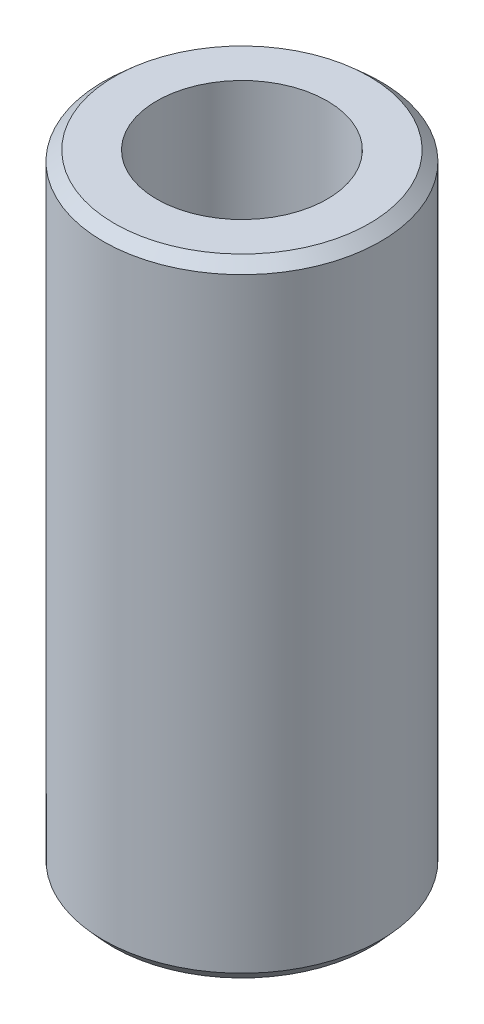
SolidWorks part; units mm, degrees
ref_plane "Front Plane" through (0, 0, 0) normal (0, 0, 1) x (1, 0, 0)
ref_plane "Top Plane" through (0, 0, 0) normal (0, 1, 0) x (1, 0, 0)
ref_plane "Right Plane" through (0, 0, 0) normal (1, 0, 0) x (0, 0, -1)
sketch "Sketch1" plane through (0, 0, 0) normal (0, 1, 0) x (1, 0, 0)
  circle A0 centre (0, 0) radius 20
  dimension "SHAFT_OD" = 40
extrude "Boss-Extrude1" add sketch "Sketch1" along normal blind 90.3574
sketch "Sketch2" plane through (0, 0, 0) normal (0, 1, 0) x (1, 0, 0)
  circle A0 centre (0, 0) radius 12.2946
  dimension "BORE_D" = 24.5892
extrude "Cut-Extrude1" cut sketch "Sketch2" along normal through all
chamfer "Chamfer1" distance 1.4382 angle 48.24 2 edges at (0, 90.3574, 20) (0, 0, 20) first distance on face at (0, 90.3574, 20) first distance on face at (0, 0, 12.2946)
